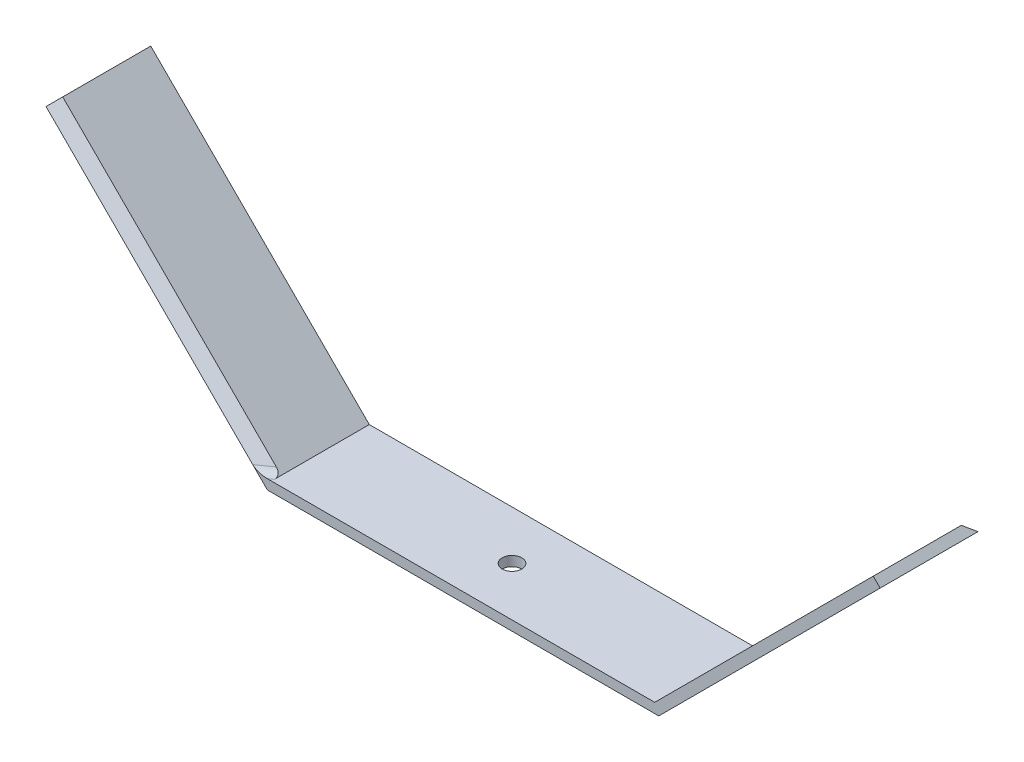
SolidWorks part; units mm, degrees
ref_plane "Front Plane" through (0, 0, 0) normal (0, 0, 1) x (1, 0, 0)
ref_plane "Top Plane" through (0, 0, 0) normal (0, 1, 0) x (1, 0, 0)
ref_plane "Right Plane" through (0, 0, 0) normal (1, 0, 0) x (0, 0, -1)
sketch "Sketch1" plane through (0, 0, 0) normal (0, 0, 1) x (1, 0, 0)
  line L0 (20, 0) -> (-20, 0)
  line L1 (-20, 0) -> (-42.6274, 22.6274)
  line L2 (-42.6274, 22.6274) -> (-41.9203, 23.3345)
  line L3 (-41.9203, 23.3345) -> (-19.5858, 1)
  line L4 (-19.5858, 1) -> (19.5858, 1)
  line L5 (0, 1) -> (0, 0) construction
  line L6 (20, 0) -> (42.6274, 22.6274)
  line L7 (42.6274, 22.6274) -> (41.9203, 23.3345)
  line L8 (41.9203, 23.3345) -> (19.5858, 1)
  dimension "D1" = 1
  dimension "D3" = 135
  dimension "D4" = 90
  dimension "D5" = 32
  dimension "D6" = 20
  dimension "D7" = 1
extrude "Blade Extrude" add sketch "Sketch1" along normal blind 10
chamfer "Blade Cut" distance 1 angle 45 2 edges at (30.753, 12.1673, 0) (-30.753, 12.1673, 10)
fillet "Edge Rounding" radius 1 2 edges at (20.2929, 1, 0.5) (-20.2929, 1, 9.5)
sketch "Sketch2" plane through (0, 1, 0) normal (0, 1, 0) x (1, 0, 0)
  line L0 (0, 0) -> (0, -10) construction
  line L1 (19.5858, -10) -> (-20, -10) construction
  circle A0 centre (0, -5) radius 1
  dimension "D1" = 2
extrude "Hole for Screw (Blade)" cut sketch "Sketch2" against normal blind 10
